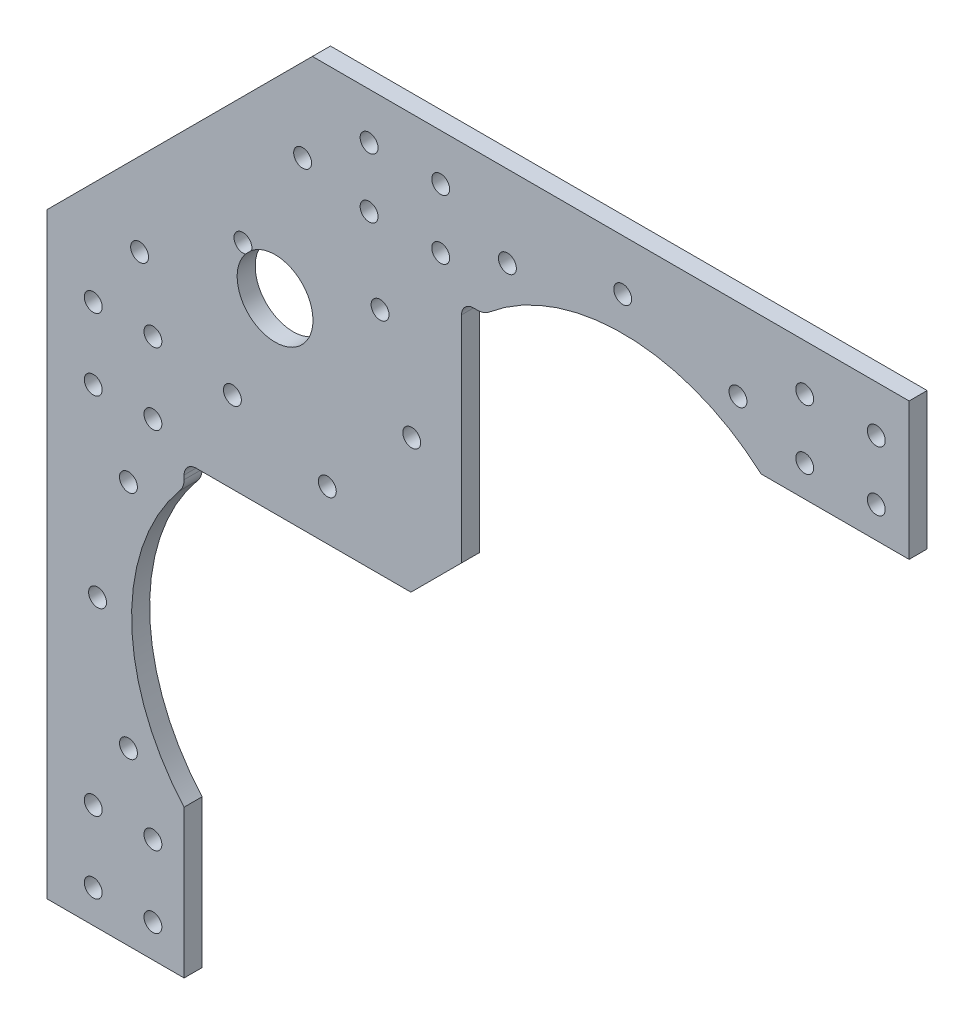
SolidWorks part; units mm, degrees
ref_plane "Front Plane" through (0, 0, 0) normal (0, 0, 1) x (1, 0, 0)
ref_plane "Top Plane" through (0, 0, 0) normal (0, 1, 0) x (1, 0, 0)
ref_plane "Right Plane" through (0, 0, 0) normal (1, 0, 0) x (0, 0, -1)
sketch "Sketch1" plane through (0, 0, 0) normal (0, 0, 1) x (1, 0, 0)
  line L0 (0, 0) -> (0, 73.5) construction
  line L1 (-96.5, -48) -> (-73.5, -48)
  line L2 (-96.5, -48) -> (-96.5, 52)
  line L4 (-73.5, -48) -> (-73.5, 27) construction
  line L5 (-52, 96.5) -> (48, 96.5)
  line L7 (-27, 73.5) -> (48, 73.5) construction
  line L8 (48, 96.5) -> (48, 73.5)
  line L9 (0, 0) -> (-73.5, 0) construction
  line L10 (-27, 73.5) -> (-73.5, 27) construction
  line L11 (-73.5, 73.5) -> (-27, 73.5) construction
  line L12 (-73.5, 27) -> (-73.5, 73.5) construction
  line L13 (-52, 96.5) -> (-96.5, 52)
  line L14 (-96.5, 96.5) -> (-52, 96.5) construction
  line L15 (-96.5, 52) -> (-96.5, 96.5) construction
  line L16 (-24.3179, 73.5) -> (-25, 73.5)
  line L17 (23.2069, 73.5) -> (48, 73.5)
  line L18 (-73.5, 25) -> (-73.5, 24.3179)
  line L19 (-73.5, -48) -> (-73.5, -23.2069)
  line L20 (-73.5, 23.2069) -> (-73.5, -23.2069) construction
  line L21 (-23.2069, 73.5) -> (23.2069, 73.5) construction
  line L22 (-71.5, 27) -> (-35.4853, 27)
  line L23 (-27, 35.4853) -> (-27, 71.5)
  line L24 (-35.4853, 27) -> (-27, 35.4853)
  line L25 (-25, 73.5) -> (-27, 73.5) construction
  line L26 (-27, 71.5) -> (-27, 73.5) construction
  line L27 (-73.5, 27) -> (-73.5, 25) construction
  line L28 (-73.5, 27) -> (-71.5, 27) construction
  line L29 (-23.2069, 73.5) -> (-24.3179, 73.5) construction
  line L30 (-73.5, 24.3179) -> (-73.5, 23.2069) construction
  arc A0 (23.2069, 73.5) -> (-22.3981, 74.1947) centre (0, 47.3) ccw
  arc A1 (-74.1947, 22.3981) -> (-73.5, -23.2069) centre (-47.3, 0) ccw
  arc A2 (-25, 73.5) -> (-27, 71.5) centre (-25, 71.5) ccw
  arc A3 (-71.5, 27) -> (-73.5, 25) centre (-71.5, 25) ccw
  arc A4 (-24.3179, 73.5) -> (-22.3981, 74.1947) centre (-24.3179, 76.5) ccw
  arc A5 (-22.3981, 74.1947) -> (-23.2069, 73.5) centre (0, 47.3) ccw construction
  arc A6 (-73.5, 24.3179) -> (-74.1947, 22.3981) centre (-76.5, 24.3179) cw
  arc A7 (-73.5, 23.2069) -> (-74.1947, 22.3981) centre (-47.3, 0) ccw construction
  dimension "D6" = 35
  dimension "D10" = 2
  dimension "D11" = 3
  dimension "D1" = 135
  dimension "D2" = 23
  dimension "D3" = 73.5
  dimension "D4" = 48
  dimension "D8" = 27
  dimension "D9" = 12
  dimension "D5" = 100
  dimension "D7" = 26.2
extrude "Boss-Extrude1" add sketch "Sketch1" along normal blind 3.0226
ref_axis "Axis1" through (0, 0, -0.1511) along (0, 0, 1)
sketch "Sketch3" plane through (0, 0, 3.0226) normal (0, 0, 1) x (1, 0, 0)
  line L1 (30.5, 88.7259) -> (30.5, 78.7259) construction
  line L2 (30.5, 88.7259) -> (42.5, 88.7259) construction
  line L3 (42.5, 88.7259) -> (42.5, 78.7259) construction
  line L4 (30.5, 78.7259) -> (42.5, 78.7259) construction
  line L16 (-30.5, 78.7259) -> (0, 78.7259) construction
  line L17 (0, 78.7259) -> (0, 0) construction
  line L18 (0, 78.7259) -> (30.5, 78.7259) construction
  line L19 (-78.7259, 0) -> (0, 0) construction
  line L20 (-78.7259, -30.5) -> (-78.7259, 0) construction
  line L21 (-78.7259, 0) -> (-78.7259, 30.5) construction
  line L30 (-42.5, 88.7259) -> (-42.5, 78.7259) construction
  line L31 (-42.5, 88.7259) -> (-30.5, 88.7259) construction
  line L32 (-30.5, 88.7259) -> (-30.5, 78.7259) construction
  line L33 (-42.5, 78.7259) -> (-30.5, 78.7259) construction
  line L34 (-88.7259, 42.5) -> (-88.7259, 30.5) construction
  line L35 (-88.7259, 42.5) -> (-78.7259, 42.5) construction
  line L36 (-78.7259, 42.5) -> (-78.7259, 30.5) construction
  line L37 (-88.7259, 30.5) -> (-78.7259, 30.5) construction
  line L38 (-88.7259, -30.5) -> (-88.7259, -42.5) construction
  line L39 (-88.7259, -30.5) -> (-78.7259, -30.5) construction
  line L40 (-78.7259, -30.5) -> (-78.7259, -42.5) construction
  line L41 (-88.7259, -42.5) -> (-78.7259, -42.5) construction
  circle A0 centre (30.5, 78.7259) radius 1.5
  circle A1 centre (30.5, 88.7259) radius 1.5
  circle A2 centre (42.5, 88.7259) radius 1.5
  circle A3 centre (42.5, 78.7259) radius 1.5
  circle A24 centre (-42.5, 78.7259) radius 1.5
  circle A25 centre (-42.5, 88.7259) radius 1.5
  circle A26 centre (-30.5, 88.7259) radius 1.5
  circle A27 centre (-30.5, 78.7259) radius 1.5
  circle A28 centre (-88.7259, 30.5) radius 1.5
  circle A29 centre (-88.7259, 42.5) radius 1.5
  circle A30 centre (-78.7259, 42.5) radius 1.5
  circle A31 centre (-78.7259, 30.5) radius 1.5
  circle A32 centre (-88.7259, -42.5) radius 1.5
  circle A33 centre (-88.7259, -30.5) radius 1.5
  circle A34 centre (-78.7259, -30.5) radius 1.5
  circle A35 centre (-78.7259, -42.5) radius 1.5
  dimension "D1" = 3
  dimension "D8" = 30.5
  dimension "D2" = 12
  dimension "D6" = 10
  dimension "D3" = 78.7259
extrude "Cut-Extrude1" cut sketch "Sketch3" against normal blind 10
sketch "Sketch4" plane through (0, 0, 3.0226) normal (0, 0, 1) x (1, 0, 0)
  line L0 (0, 0) -> (0, 88) construction
  line L1 (0, 0) -> (-63.6396, 63.6396) construction
  line L2 (0, 0) -> (-88, 0) construction
  line L3 (-82.8236, 19.3185) -> (-88, 0) construction
  line L4 (-88, 0) -> (-82.8236, -19.3185) construction
  line L5 (-80.9601, 53.6396) -> (-63.6396, 63.6396) construction
  line L6 (-63.6396, 63.6396) -> (-83.2677, 83.2677) construction
  line L7 (-19.3185, 82.8236) -> (0, 88) construction
  line L8 (-65.4074, 40.6586) -> (-40.6586, 65.4074) construction
  line L9 (-35.3553, 49.4975) -> (-49.4975, 35.3553) construction
  line L10 (-73.5, -48) -> (-73.5, -23.2069) construction
  line L11 (-35.4853, 27) -> (-27, 35.4853) construction
  circle A0 centre (-88, 0) radius 1.5
  circle A1 centre (-63.6396, 63.6396) radius 1.5
  circle A2 centre (0, 88) radius 1.5
  circle A3 centre (-80.9601, 53.6396) radius 1.5
  circle A4 centre (-53.6396, 80.9601) radius 1.5
  circle A5 centre (19.3185, 82.8236) radius 1.5
  circle A6 centre (-19.3185, 82.8236) radius 1.5
  circle A7 centre (-82.8236, 19.3185) radius 1.5
  circle A8 centre (-82.8236, -19.3185) radius 1.5
  circle A9 centre (-40.6586, 65.4074) radius 1.5
  circle A10 centre (-65.4074, 40.6586) radius 1.5
  circle A11 centre (-49.4975, 35.3553) radius 1.5
  circle A12 centre (-35.3553, 49.4975) radius 1.5
  dimension "D2" = 3
  dimension "D1" = 45
  dimension "D3" = 14.5
  dimension "D4" = 75
  dimension "D5" = 20
  dimension "D6" = 45.8162
  dimension "D7" = 75
  dimension "D8" = 75
  dimension "D9" = 35
  dimension "D10" = 20
  dimension "D11" = 15
  dimension "D12" = 15
extrude "Cut-Extrude2" cut sketch "Sketch4" against normal through all
ref_plane "Plane1" through (0, 0, 0) normal (-0.7071, -0.7071, 0) x (-0.7071, 0.7071, 0)
sketch "Sketch5" plane through (0, 0, 3.0226) normal (0, 0, 1) x (1, 0, 0)
  circle A0 centre (-58.2568, 58.2565) radius 6.35
  point P2 (-58.0762, 58.076)
  point P3 (-58.2664, 58.248)
  point P4 (-58.7751, 58.3772)
  point P5 (-58.2633, 58.263)
  point P7 (0, 0)
  dimension "D1" = 12.7
extrude "Cut-Extrude3" cut sketch "Sketch5" against normal through all both and the other way through all
equation "\"EyeDiameter\" = 35"
equation "\"BasePlaneDistance\" = \"EyeDiameter\"/2+19.84"
equation "\"EyeClearance\" = 2"
equation "\"L2Thickness\" = 8"
equation "\"L2_ID\" = 20"
equation "\"Offset\"= - 2"
equation "\"D3@Sketch1\"=\"BasePlaneDistance\" + 38.16 +\"Offset\""
equation "\"D3@Sketch3\"=\"BasePlaneDistance\" - 37.34+78.72592343"
equation "\"D7@Sketch1\"=24.20 - \"Offset\""
equation "\"D2@Sketch1\"=25.00 + \"Offset\""
